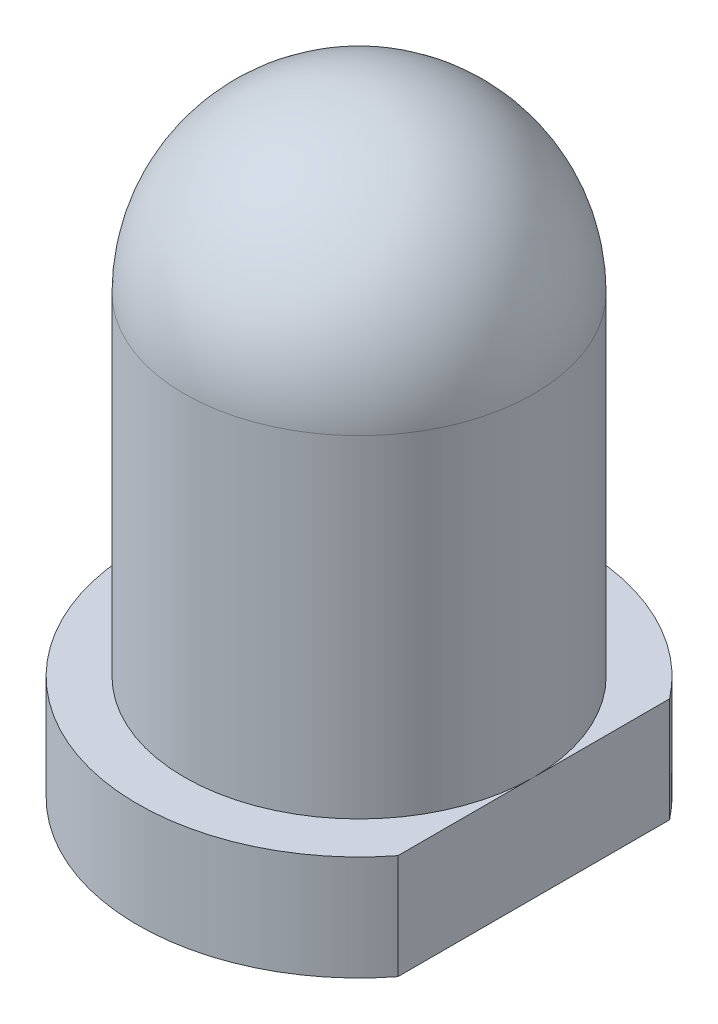
SolidWorks part; units mm, degrees
ref_plane "Front Plane" through (0, 0, 0) normal (0, 0, 1) x (1, 0, 0)
ref_plane "Top Plane" through (0, 0, 0) normal (0, 1, 0) x (1, 0, 0)
ref_plane "Right Plane" through (0, 0, 0) normal (1, 0, 0) x (0, 0, -1)
sketch "Body Profile" plane through (0, 0, 0) normal (0, 0, 1) x (1, 0, 0)
  line L0 (0, -170.0139) -> (0, 8330.6815) construction
  line L1 (1.5, 2.85) -> (1.5, 0)
  line L2 (0, 0) -> (1.5, 0)
  line L3 (0, 4.35) -> (0, 0)
  line L4 (-1.5, 2.85) -> (-1.5, 0) construction
  line L5 (0, 0) -> (-1.5, 0) construction
  arc A0 (1.5, 2.85) -> (0, 4.35) centre (0, 2.85) ccw
  arc A1 (0, 4.35) -> (-1.5, 2.85) centre (0, 2.85) ccw construction
  dimension "Height" = 4.35
  dimension "Diameter" = 3
revolve "Body" add sketch "Body Profile" angle 360 about L0
sketch "Flange Outline" plane through (0, 0, 0) normal (0, -1, 0) x (1, 0, 0)
  line L0 (1.5, -1.1662) -> (1.5, 1.1662)
  arc A0 (1.5, 1.1662) -> (1.5, -1.1662) centre (0, 0) ccw
  circle A2 centre (0, 0) radius 1.5 construction
  dimension "Diameter" = 3.8
extrude "Flange" add sketch "Flange Outline" along normal blind 0.9
ref_axis "Center line" through (0, 2.85, 0) along (0, -1, 0)
